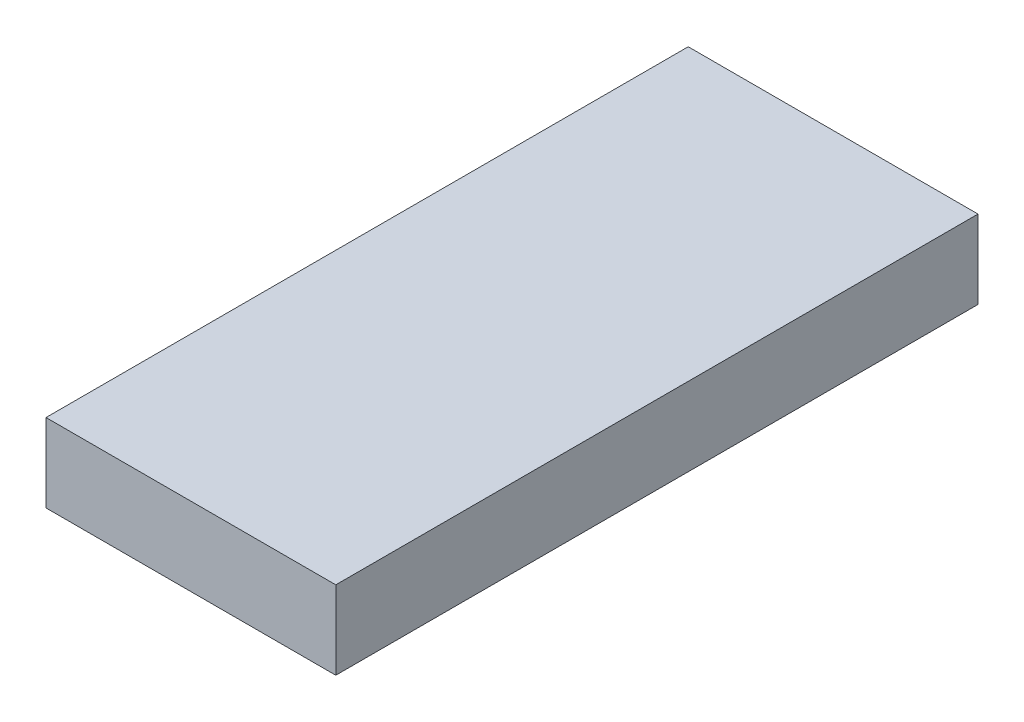
SolidWorks part; units mm, degrees
ref_plane "Front Plane" through (0, 0, 0) normal (0, 0, 1) x (1, 0, 0)
ref_plane "Top Plane" through (0, 0, 0) normal (0, 1, 0) x (1, 0, 0)
ref_plane "Right Plane" through (0, 0, 0) normal (1, 0, 0) x (0, 0, -1)
sketch "Sketch1" plane through (0, 0, 0) normal (0, 1, 0) x (1, 0, 0)
  line L1 (-9.25, 20.5) -> (9.25, 20.5)
  line L2 (-9.25, 20.5) -> (-9.25, -20.5)
  line L3 (-9.25, -20.5) -> (9.25, -20.5)
  line L4 (9.25, 20.5) -> (9.25, -20.5)
  line L5 (-9.25, 20.5) -> (9.25, -20.5) construction
  line L6 (-9.25, -20.5) -> (9.25, 20.5) construction
  point P0 (0, 0)
  dimension "D1" = 18.5
  dimension "D2" = 41
extrude "Boss-Extrude1" add sketch "Sketch1" along normal mid plane 5
